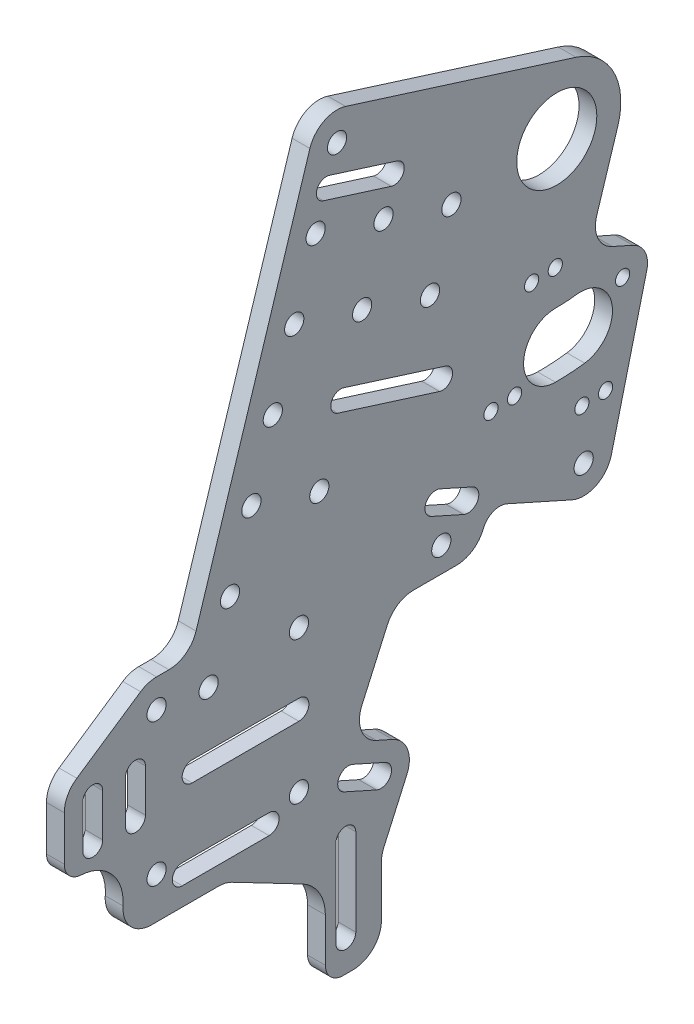
SolidWorks part; units mm, degrees
ref_plane "Front Plane" through (0, 0, 0) normal (0, 0, 1) x (1, 0, 0)
ref_plane "Top Plane" through (0, 0, 0) normal (0, 1, 0) x (1, 0, 0)
ref_plane "Right Plane" through (0, 0, 0) normal (1, 0, 0) x (0, 0, -1)
sketch "Sketch2" plane through (0, 0, 0) normal (1, 0, 0) x (0, 0, -1)
  line L3 (55, 0) -> (-55, 0) construction
  line L9 (71.6952, 111.2048) -> (68.2175, 112.7608) construction
  line L28 (0, 0) -> (-57.2178, 40.0643) construction
  line L40 (0, 0) -> (113.3671, 198.5091) construction
  line L41 (113.3671, 198.5091) -> (58.7631, 215.7257) construction
  line L42 (99.338, 182.3162) -> (24.13, 14.224) construction
  line L44 (30.078, 221.0415) -> (54.3024, 213.4035)
  line L45 (32.2166, 227.8243) -> (56.441, 220.1864)
  line L49 (104.399, 158.5001) -> (136.8581, 143.9772) construction
  line L50 (136.8581, 143.9772) -> (122.3352, 111.518) construction
  line L51 (112.8406, 159.0638) -> (145.2997, 144.5408) construction
  line L56 (43.9148, 180.4584) -> (36.2769, 156.2339) construction
  line L57 (-29.4365, 93.5262) -> (-29.4365, 42.7262) construction
  line L61 (122.3352, 111.518) -> (89.876, 126.041) construction
  line L62 (89.876, 126.041) -> (104.399, 158.5001) construction
  line L63 (104.399, 158.5001) -> (122.3352, 111.518) construction
  line L65 (145.2997, 144.5408) -> (130.7768, 112.0817) construction
  line L66 (130.7768, 112.0817) -> (98.3176, 126.6046) construction
  line L67 (98.3176, 126.6046) -> (112.8406, 159.0638) construction
  line L68 (112.8406, 159.0638) -> (130.7768, 112.0817) construction
  line L69 (58.7631, 215.7257) -> (31.1473, 224.4329) construction
  line L70 (40.5747, 41.6494) -> (37.0969, 43.2054) construction
  line L71 (38.1, 20.2565) -> (38.1, -10.7315) construction
  line L72 (41.656, 20.2565) -> (41.656, -10.7315)
  line L73 (34.544, 20.2565) -> (34.544, -10.7315)
  line L74 (0, -14.2875) -> (38.1, -14.2875) construction
  line L75 (-20.2565, 38.1) -> (10.7315, 38.1) construction
  line L76 (-20.2565, 41.656) -> (10.7315, 41.656)
  line L77 (-20.2565, 34.544) -> (10.7315, 34.544)
  line L78 (14.2875, 38.1) -> (14.2875, 0) construction
  line L79 (-52.2013, 78.1643) -> (-52.2013, 62.9243) construction
  line L80 (-48.6453, 78.1643) -> (-48.6453, 62.9243)
  line L81 (-55.7573, 78.1643) -> (-55.7573, 62.9243)
  line L82 (-36.9613, 78.1643) -> (-36.9613, 62.9243) construction
  line L83 (-33.4053, 78.1643) -> (-33.4053, 62.9243)
  line L84 (-40.5173, 78.1643) -> (-40.5173, 62.9243)
  line L85 (31.1473, 224.4329) -> (-10.8613, 91.1986) construction
  line L86 (31.1473, 224.4329) -> (34.9663, 236.5451) construction
  line L92 (27.3284, 212.3207) -> (75.7772, 197.0448) construction
  line L93 (19.6904, 188.0963) -> (68.1392, 172.8204) construction
  line L94 (36.2769, 156.2339) -> (12.0525, 163.8719) construction
  line L95 (36.2769, 156.2339) -> (72.6135, 144.777) construction
  line L96 (37.3462, 159.6254) -> (73.6828, 148.1685)
  line L97 (35.2076, 152.8425) -> (71.5442, 141.3856)
  line L98 (36.2769, 156.2339) -> (28.639, 132.0095) construction
  line L99 (28.639, 132.0095) -> (4.4146, 139.6475) construction
  line L100 (-29.4365, 68.1262) -> (-16.7365, 68.1262) construction
  line L101 (-16.7365, 68.1262) -> (21.3635, 68.1262) construction
  line L102 (-16.7365, 71.6822) -> (21.3635, 71.6822)
  line L103 (-16.7365, 64.5702) -> (21.3635, 64.5702)
  line L104 (38.0214, 246.2349) -> (120.2412, 220.3111)
  line L105 (25.2765, 239.6003) -> (-15.3369, 110.7911)
  line L106 (-29.4365, 103.6862) -> (-25.0266, 103.6862)
  line L107 (-35.1197, 101.9481) -> (-57.8844, 86.5862)
  line L108 (-62.3613, 62.2565) -> (-62.3613, 78.1643)
  line L109 (-31.257, 27.94) -> (-7.2528, 27.94)
  line L110 (30.7975, -15.5575) -> (30.7975, 0)
  line L113 (135.1691, 191.635) -> (127.6222, 167.6992)
  line L114 (133.1625, 155.37) -> (140.4889, 152.092)
  line L115 (145.4838, 141.8254) -> (132.8214, 91.067)
  line L116 (118.8141, 84.2522) -> (95.6442, 94.6189)
  line L117 (50.8, 6.3603) -> (50.8, -11.7475)
  line L118 (37.1475, -21.9075) -> (40.64, -21.9075)
  line L120 (54.7606, 42.2589) -> (48.9643, 44.8523)
  line L121 (52.9447, 78.6256) -> (43.8397, 58.2757)
  line L122 (59.8853, 28.8354) -> (51.6859, 10.5098)
  line L123 (62.2187, 84.6362) -> (77.6364, 84.6362)
  line L124 (87.2546, 91.416) -> (86.9104, 90.6468)
  line L125 (30.7975, 0) -> (15.3035, 0) construction
  line L126 (22.4684, 13.7378) -> (-2.5545, 26.7884)
  line L127 (0, 0) -> (0, 15.494) construction
  line L128 (39.0186, 38.1716) -> (50.6112, 32.9849) construction
  line L129 (70.1392, 107.727) -> (81.7318, 102.5402) construction
  line L131 (71.6952, 111.2048) -> (83.2878, 106.018)
  line L132 (68.5832, 104.2492) -> (80.1757, 99.0625)
  line L133 (40.5747, 41.6494) -> (52.1672, 36.4626)
  line L134 (37.4626, 34.6938) -> (49.0552, 29.5071)
  circle A36 centre (0, 0) radius 14.2875 construction
  circle A37 centre (-57.2178, 40.0643) radius 14.2875 construction
  circle A38 centre (113.3671, 198.5091) radius 14.2875
  arc A39 (54.3024, 213.4035) -> (56.441, 220.1864) centre (55.3717, 216.795) ccw
  arc A40 (32.2166, 227.8243) -> (30.078, 221.0415) centre (31.1473, 224.4329) ccw
  circle A49 centre (-29.4365, 42.7262) radius 3.429
  circle A50 centre (21.3635, 93.5262) radius 3.429
  circle A51 centre (122.9635, 93.5262) radius 3.429
  circle A54 centre (104.399, 158.5001) radius 2.54
  circle A55 centre (136.8581, 143.9772) radius 2.54
  circle A56 centre (122.3352, 111.518) radius 2.54
  circle A57 centre (89.876, 126.041) radius 2.54
  arc A60 (113.3671, 135.0091) -> (121.8087, 135.5727) centre (113.3671, 198.5091) ccw construction
  circle A61 centre (112.8406, 159.0638) radius 2.54
  circle A62 centre (130.7768, 112.0817) radius 2.54
  circle A63 centre (98.3176, 126.6046) radius 2.54
  circle A64 centre (-29.4365, 93.5262) radius 3.429
  circle A65 centre (21.3635, 42.7262) radius 3.429
  circle A66 centre (72.1635, 93.5262) radius 3.429
  arc A67 (41.656, 20.2565) -> (34.544, 20.2565) centre (38.1, 20.2565) ccw
  arc A68 (34.544, -10.7315) -> (41.656, -10.7315) centre (38.1, -10.7315) ccw
  arc A69 (-20.2565, 41.656) -> (-20.2565, 34.544) centre (-20.2565, 38.1) ccw
  arc A70 (10.7315, 34.544) -> (10.7315, 41.656) centre (10.7315, 38.1) ccw
  arc A71 (-48.6453, 78.1643) -> (-55.7573, 78.1643) centre (-52.2013, 78.1643) ccw
  arc A72 (-55.7573, 62.9243) -> (-48.6453, 62.9243) centre (-52.2013, 62.9243) ccw
  arc A73 (-33.4053, 78.1643) -> (-40.5173, 78.1643) centre (-36.9613, 78.1643) ccw
  arc A74 (-40.5173, 62.9243) -> (-33.4053, 62.9243) centre (-36.9613, 62.9243) ccw
  circle A75 centre (34.9663, 236.5451) radius 3.429
  circle A76 centre (27.3284, 212.3207) radius 3.429
  circle A77 centre (19.6904, 188.0963) radius 3.429
  circle A78 centre (12.0525, 163.8719) radius 3.429
  circle A79 centre (4.4146, 139.6475) radius 3.429
  circle A80 centre (-3.2234, 115.423) radius 3.429
  circle A81 centre (-10.8613, 91.1986) radius 3.429
  circle A82 centre (51.5528, 204.6828) radius 3.429
  circle A83 centre (43.9148, 180.4584) radius 3.429
  circle A84 centre (75.7772, 197.0448) radius 3.429
  circle A85 centre (68.1392, 172.8204) radius 3.429
  arc A86 (37.3462, 159.6254) -> (35.2076, 152.8425) centre (36.2769, 156.2339) ccw
  arc A87 (71.5442, 141.3856) -> (73.6828, 148.1685) centre (72.6135, 144.777) ccw
  circle A88 centre (28.639, 132.0095) radius 3.429
  arc A89 (-16.7365, 71.6822) -> (-16.7365, 64.5702) centre (-16.7365, 68.1262) ccw
  arc A90 (21.3635, 64.5702) -> (21.3635, 71.6822) centre (21.3635, 68.1262) ccw
  arc A91 (38.0214, 246.2349) -> (25.2765, 239.6003) centre (34.9663, 236.5451) ccw
  arc A92 (120.2412, 220.3111) -> (135.1691, 191.635) centre (113.3671, 198.5091) cw
  arc A93 (-35.1197, 101.9481) -> (-29.4365, 103.6862) centre (-29.4365, 93.5262) cw
  arc A94 (-62.3613, 78.1643) -> (-57.8844, 86.5862) centre (-52.2013, 78.1643) cw
  arc A95 (-25.0266, 103.6862) -> (-15.3369, 110.7911) centre (-25.0266, 113.8462) ccw
  arc A96 (-56.356, 55.9159) -> (-62.3613, 62.2565) centre (-56.0113, 62.2565) cw
  arc A97 (-41.388, 38.8666) -> (-56.356, 55.9159) centre (-57.2178, 40.0643) ccw
  arc A99 (-31.257, 27.94) -> (-41.388, 38.8666) centre (-31.257, 38.1) cw
  arc A100 (37.1475, -21.9075) -> (30.7975, -15.5575) centre (37.1475, -15.5575) cw
  arc A101 (140.4889, 152.092) -> (145.4838, 141.8254) centre (136.8581, 143.9772) cw
  arc A102 (132.8214, 91.067) -> (118.8141, 84.2522) centre (122.9635, 93.5262) cw
  arc A105 (133.1625, 155.37) -> (127.6222, 167.6992) centre (137.3119, 164.644) cw
  arc A106 (121.8087, 135.5727) -> (112.9541, 135.0104) centre (113.3671, 198.5091) cw construction
  arc A107 (112.8797, 123.5807) -> (123.3282, 124.2442) centre (113.3671, 198.5091) ccw
  arc A108 (113.0284, 146.4402) -> (120.2892, 146.9013) centre (113.3671, 198.5091) ccw
  arc A109 (113.0284, 146.4402) -> (112.8797, 123.5807) centre (112.9541, 135.0104) ccw
  arc A110 (123.3282, 124.2442) -> (120.2892, 146.9013) centre (121.8087, 135.5727) ccw
  arc A111 (40.64, -21.9075) -> (50.8, -11.7475) centre (40.64, -11.7475) ccw
  arc A112 (50.8, 6.3603) -> (51.6859, 10.5098) centre (60.96, 6.3603) cw
  arc A113 (54.7606, 42.2589) -> (59.8853, 28.8354) centre (50.6112, 32.9849) cw
  arc A114 (48.9643, 44.8523) -> (43.8397, 58.2757) centre (53.1137, 54.1263) cw
  arc A115 (62.2187, 84.6362) -> (52.9447, 78.6256) centre (62.2187, 74.4762) ccw
  arc A117 (77.6364, 84.6362) -> (86.9104, 90.6468) centre (77.6364, 94.7962) ccw
  arc A118 (87.2546, 91.416) -> (95.6442, 94.6189) centre (93.0509, 88.8226) cw
  arc A121 (30.7975, 0) -> (22.4684, 13.7378) centre (15.3035, 0) ccw
  arc A122 (-7.2528, 27.94) -> (-2.5545, 26.7884) centre (-7.2528, 17.78) cw
  arc A126 (71.6952, 111.2048) -> (68.5832, 104.2492) centre (70.1392, 107.727) ccw
  arc A127 (80.1757, 99.0625) -> (83.2878, 106.018) centre (81.7318, 102.5402) ccw
  arc A128 (40.5747, 41.6494) -> (37.4626, 34.6938) centre (39.0186, 38.1716) ccw
  arc A129 (49.0552, 29.5071) -> (52.1672, 36.4626) centre (50.6112, 32.9849) ccw
  point P26 (66.6614, 109.283)
  point P30 (0, 0)
  point P31 (113.3671, 135.0091)
  point P37 (2.3135, 68.1262)
  point P38 (35.5409, 39.7276)
  point P40 (75.9355, 105.1336)
  point P43 (44.8149, 35.5782)
  point P59 (0, 0)
  point P60 (0, 0)
  point P61 (0, 0)
  point P70 (54.4452, 150.5055)
  point P80 (121.8087, 135.5727)
  point P89 (38.1, 4.7625)
  point P98 (-4.7625, 38.1)
  point P100 (38.1, 23.8125)
  point P109 (-23.8125, 38.1)
  point P111 (-52.2013, 70.5443)
  point P116 (-36.9613, 70.5443)
  point P176 (117.3912, 135.1367)
  point P179 (-4.7625, 27.94)
  point P201 (64.0347, 38.1095)
  point P204 (39.6903, 49.0017)
  dimension "D1" = 28.575
  dimension "D2" = 69.85
  dimension "D5" = 25.4
  dimension "D6" = 3.556
  dimension "D7" = 184.15
  dimension "D8" = 28.0103
  dimension "D9" = 7.62
  dimension "D10" = 10.16
  dimension "D11" = 27.7812
  dimension "D13" = 6.858
  dimension "D15" = 53.4619
  dimension "D17" = 180.1812
  dimension "D18" = 53.4619
  dimension "D19" = 3.556
  dimension "D20" = 38.1
  dimension "D21" = 38.1
  dimension "D24" = 5.08
  dimension "D28" = 10.16
  dimension "D30" = 35.56
  dimension "D31" = 8.4416
  dimension "D33" = 65.895
  dimension "D34" = 35
  dimension "D35" = 60.27
  dimension "D40" = 76.2
  dimension "D16" = 7.62
  dimension "D27" = 10.16
  dimension "D47" = 38.1
  dimension "D48" = 7.112
  dimension "D50" = 38.1
  dimension "D53" = 3.556
  dimension "D56" = 12.7
  dimension "D57" = 12.7
  dimension "D58" = 25.4
  dimension "D60" = 25.4
  dimension "D61" = 25.4
  dimension "D25" = 3.556
  dimension "D63" = 6.35
  dimension "D64" = 31.75
  dimension "D65" = 10.16
  dimension "D69" = 16.51
  dimension "D70" = 12.7
  dimension "D73" = 6.35
  dimension "D74" = 8.89
  dimension "D72" = 8.89
  dimension "D75" = 11.43
  dimension "D77" = 7.2813
  dimension "D78" = 15.494
  dimension "D81" = 15.494
  dimension "D82" = 10.16
  dimension "D83" = 6.35
  dimension "D38" = 17.7847
  dimension "D3" = 228.6
  dimension "D12" = 2.6619
  dimension "D14" = 78.5812
  dimension "D22" = 35.56
  dimension "D23" = 63.5
  dimension "D26" = 12.7
  dimension "D29" = 8.4667
  dimension "D32" = 50.8
  dimension "D36" = 16.1929
  dimension "D37" = 12.7
  dimension "D39" = 76.2
  dimension "D41" = 12.7
  dimension "D43" = 17.5
  dimension "D44" = 7.112
  dimension "D45" = 3.556
  dimension "D46" = 38.1
  dimension "D49" = 38.1
  dimension "D51" = 15.24
  dimension "D52" = 15.24
  dimension "D54" = 38.1
  dimension "D55" = 23.8125
  dimension "D59" = 25.4
  dimension "D62" = 25.4
  dimension "D66" = 15.494
  dimension "D67" = 3
  dimension "D68" = 25.4
  dimension "D71" = 7.62
  dimension "D76" = 60.8098
extrude "Boss-Extrude1" add sketch "Sketch2" along normal blind 3.175 and the other way blind 3.175
sketch "Sketch3" plane through (3.175, 0, 0) normal (1, 0, 0) x (0, 0, -1)
  text T0 "3597" font "A4 SPEED" height 11.43
  dimension "D1" = 106.68
  dimension "D2" = 5.08
extrude "Cut-Extrude1" [suppressed] cut sketch "Sketch3" against normal through all
